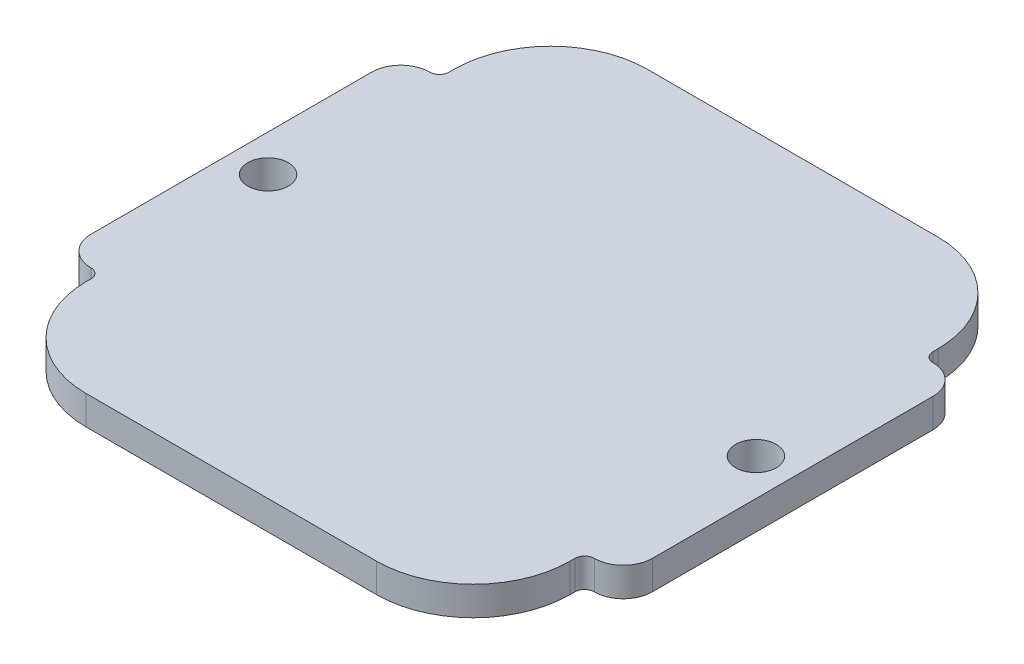
SolidWorks part; units mm, degrees
ref_plane "Front Plane" through (0, 0, 0) normal (0, 0, 1) x (1, 0, 0)
ref_plane "Top Plane" through (0, 0, 0) normal (0, 1, 0) x (1, 0, 0)
ref_plane "Right Plane" through (0, 0, 0) normal (1, 0, 0) x (0, 0, -1)
sketch "Sketch1" plane through (0, 0, 0) normal (0, 1, 0) x (1, 0, 0)
  line L0 (29, -17.5) -> (25, -17.5)
  line L1 (-25, 29) -> (25, 29)
  line L2 (-29, 17.5) -> (-29, -17.5)
  line L3 (-25, -29) -> (25, -29)
  line L4 (29, 17.5) -> (29, -17.5)
  line L5 (-25, 25) -> (25, -25) construction
  line L6 (-25, -25) -> (25, 25) construction
  line L7 (25, -17.5) -> (25, -29)
  line L8 (29, 17.5) -> (25, 17.5)
  line L9 (25, 17.5) -> (25, 29)
  line L10 (-25, 17.5) -> (-29, 17.5)
  line L11 (-25, 17.5) -> (-25, 29)
  line L12 (-29, -17.5) -> (-25, -17.5)
  line L13 (-25, -17.5) -> (-25, -29)
  point P0 (0, 0)
  dimension "D1" = 35
  dimension "D2" = 50
  dimension "D3" = 4
  dimension "D4" = 4
  dimension "D5" = 4
  dimension "D6" = 4
  dimension "D7" = 11.5
  dimension "D8" = 11.5
  dimension "D9" = 11.5
extrude "Boss-Extrude1" add sketch "Sketch1" along normal blind 3
fillet "Fillet1" radius 10 4 edges at (25, 1.5, -29) (25, 1.5, 29) (-25, 1.5, 29) (-25, 1.5, -29)
fillet "Fillet2" radius 1 4 edges at (-25, 1.5, 17.5) (25, 1.5, 17.5) (25, 1.5, -17.5) (-25, 1.5, -17.5)
fillet "Fillet3" radius 3 4 edges at (29, 1.5, 17.5) (29, 1.5, -17.5) (-29, 1.5, 17.5) (-29, 1.5, -17.5)
sketch "Sketch2" plane through (0, 3, 0) normal (0, 1, 0) x (1, 0, 0)
  line L0 (-29, 14.5) -> (-29, -14.5) construction
  line L1 (29, -14.5) -> (29, 14.5) construction
  circle A0 centre (-25.2, 0) radius 2.1
  circle A1 centre (25.2, 0) radius 2.1
  dimension "D1" = 4.2
  dimension "D2" = 4.2
  dimension "D3" = 3.8
  dimension "D4" = 3.8
extrude "Cut-Extrude1" cut sketch "Sketch2" against normal through all
